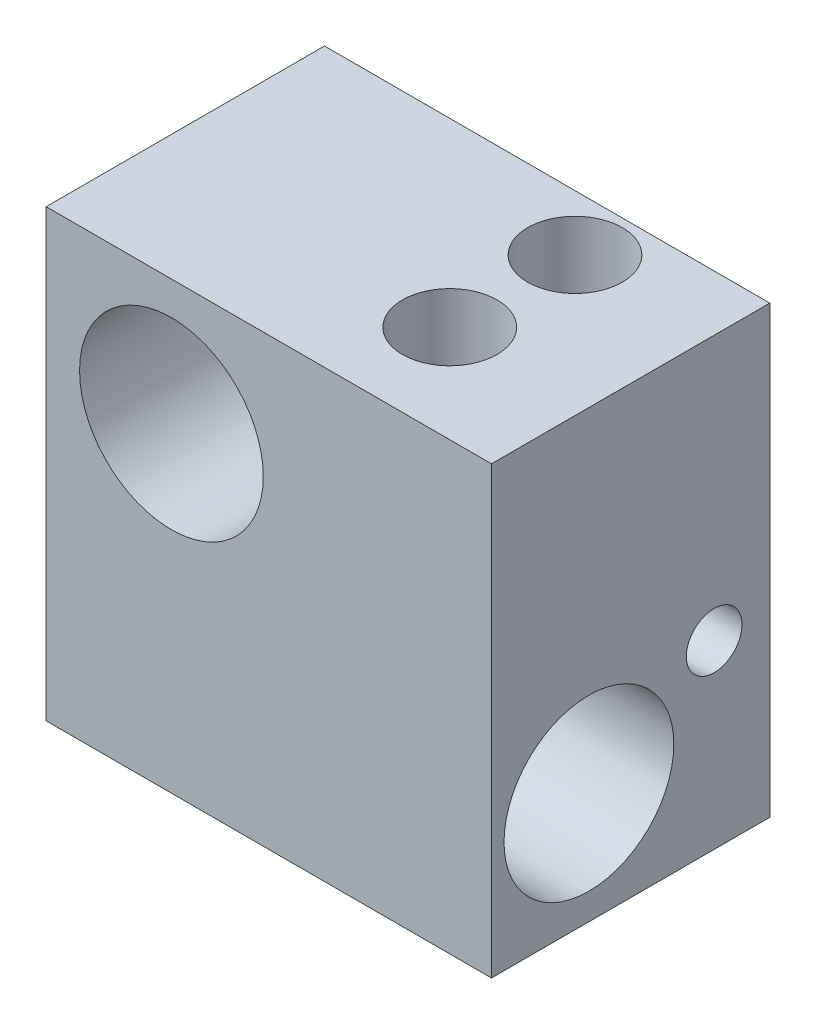
SolidWorks part; units mm, degrees
material "3.1325 (EN-AW 2017A)"
ref_plane "Plan de face" through (0, 0, 0) normal (0, 0, 1) x (1, 0, 0)
ref_plane "Plan de dessus" through (0, 0, 0) normal (0, 1, 0) x (1, 0, 0)
ref_plane "Plan de droite" through (0, 0, 0) normal (1, 0, 0) x (0, 0, -1)
sketch "Esquisse1" plane through (0, 0, 0) normal (0, 0, 1) x (1, 0, 0)
  line L1 (0, 0) -> (16, 0)
  line L2 (0, 0) -> (0, 16)
  line L3 (0, 16) -> (16, 16)
  line L4 (16, 0) -> (16, 16)
  dimension "D1" = 16
  dimension "D2" = 16
extrude "Boss.-Extru.1" add sketch "Esquisse1" along normal blind 10
sketch "Esquisse2" plane through (0, 0, 10) normal (0, 0, 1) x (1, 0, 0)
  line L0 (16, 16) -> (0, 16) construction
  line L2 (0, 16) -> (0, 0) construction
  circle A0 centre (4.5, 11.5) radius 3
  dimension "D1" = 6
  dimension "D2" = 4.5
  dimension "D3" = 4.5
hole_wizard "Dégagement M61" positions "Esquisse4" profile "Esquisse3" hole size "M6" standard "ISO" end condition through all
sketch "Esquisse4" plane through (0, 0, 10) normal (0, 0, 1) x (1, 0, 0)
  point P0 (4.5, 11.5)
sketch "Esquisse3" plane through (4.5, 11.5, 10) normal (1, 0, 0) x (0, -1, 0)
  line L0 (0, 0) -> (0, 10)
  line L1 (0, 10) -> (3.3, 10)
  line L2 (3.3, 10) -> (3.3, 0)
  line L5 (3.3, 0) -> (0, 0)
  line L11 (0, -6.35) -> (0, 107.95) construction
  dimension "Diamètre du perçage jusqu'au prochain" = 6.6
  dimension "Profondeur du perçage jusqu'au prochain" = 10
sketch "Esquisse5" plane through (16, 0, 0) normal (1, 0, 0) x (0, 0, -1)
  line L0 (-10, 0) -> (0, 0) construction
  line L1 (-10, 0) -> (-10, 16) construction
  line L2 (0, 0) -> (0, 16) construction
  circle A0 centre (-6.5, 4) radius 3
  circle A1 centre (-2, 6.5) radius 1
  dimension "D1" = 6
  dimension "D2" = 2
  dimension "D3" = 4
  dimension "D4" = 3.5
  dimension "D5" = 2
  dimension "D6" = 6.5
hole_wizard "Diamètre du perçage Ø6.1 (6.1)1" positions "Esquisse7" profile "Esquisse6" hole size "Ø6.1" standard "ISO" end condition through all
sketch "Esquisse7" plane through (16, 0, 0) normal (1, 0, 0) x (0, 0, -1)
  point P0 (-6.5, 4)
sketch "Esquisse6" plane through (16, 4, 6.5) normal (0, 1, 0) x (0, 0, -1)
  line L0 (0, 0) -> (0, 16)
  line L1 (0, 16) -> (3.05, 16)
  line L2 (3.05, 16) -> (3.05, 0)
  line L5 (3.05, 0) -> (0, 0)
  line L11 (0, -6.35) -> (0, 107.95) construction
  dimension "Diamètre du perçage jusqu'au prochain" = 6.1
  dimension "Profondeur du perçage jusqu'au prochain" = 16
hole_wizard "Diamètre du perçage Ø2.0 (2)1" positions "Esquisse9" profile "Esquisse8" hole size "Ø2.0" standard "ISO" end condition through all
sketch "Esquisse9" plane through (16, 0, 0) normal (1, 0, 0) x (0, 0, -1)
  point P0 (-2, 6.5)
sketch "Esquisse8" plane through (16, 6.5, 2) normal (0, 1, 0) x (0, 0, -1)
  line L0 (0, 0) -> (0, 16)
  line L1 (0, 16) -> (1, 16)
  line L2 (1, 16) -> (1, 0)
  line L5 (1, 0) -> (0, 0)
  line L11 (0, -6.35) -> (0, 107.95) construction
  dimension "Diamètre du perçage jusqu'au prochain" = 2
  dimension "Profondeur du perçage jusqu'au prochain" = 16
sketch "Esquisse10" plane through (0, 16, 0) normal (0, 1, 0) x (1, 0, 0)
  line L0 (16, -10) -> (16, 0) construction
  line L1 (16, -10) -> (0, -10) construction
  line L2 (16, 0) -> (0, 0) construction
  circle A0 centre (11, -6.5) radius 1.5
  circle A1 centre (11, -2) radius 1.5
  dimension "D1" = 3
  dimension "D2" = 3
  dimension "D3" = 5
  dimension "D4" = 5
  dimension "D5" = 3.5
  dimension "D6" = 2
hole_wizard "Dégagement M31" positions "Esquisse14" profile "Esquisse13" hole size "M3" standard "ISO"
sketch "Esquisse14" plane through (0, 16, 0) normal (0, 1, 0) x (1, 0, 0)
  point P0 (11, -6.5)
sketch "Esquisse13" plane through (11, 16, 6.5) normal (1, 0, 0) x (0, 0, 1)
  line L0 (0, 0) -> (0, 10)
  line L1 (0, 10) -> (1.7, 10)
  line L2 (1.7, 10) -> (1.7, 0)
  line L5 (1.7, 0) -> (0, 0)
  line L10 (0, 10) -> (-1.7, 10) construction
  line L11 (0, -6.35) -> (0, 107.95) construction
  dimension "Diamètre du perçage" = 3.4
  dimension "Profondeur du perçage" = 10
  dimension "Angle de pointe" = 180
hole_wizard "Dégagement M32" positions "Esquisse16" profile "Esquisse15" hole size "M3" standard "ISO"
sketch "Esquisse16" plane through (0, 16, 0) normal (0, 1, 0) x (1, 0, 0)
  point P0 (11, -2)
sketch "Esquisse15" plane through (11, 16, 2) normal (1, 0, 0) x (0, 0, 1)
  line L0 (0, 0) -> (0, 9.5)
  line L1 (0, 9.5) -> (1.7, 9.5)
  line L2 (1.7, 9.5) -> (1.7, 0)
  line L5 (1.7, 0) -> (0, 0)
  line L10 (0, 9.5) -> (-1.7, 9.5) construction
  line L11 (0, -6.35) -> (0, 107.95) construction
  dimension "Diamètre du perçage" = 3.4
  dimension "Profondeur du perçage" = 9.5
  dimension "Angle de pointe" = 180
chamfer "Chanfrein1" [suppressed] distance 0.25 angle 45
